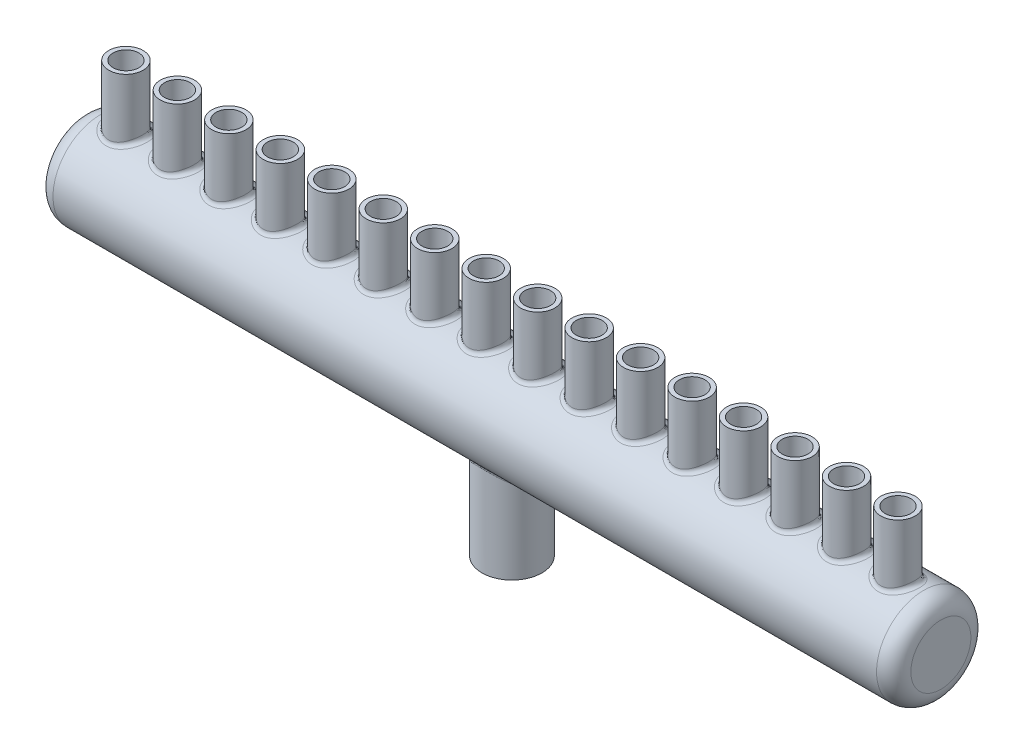
SolidWorks part; units mm, degrees
ref_plane "Alzado" through (0, 0, 0) normal (0, 0, 1) x (1, 0, 0)
ref_plane "Planta" through (0, 0, 0) normal (0, 1, 0) x (1, 0, 0)
ref_plane "Vista lateral" through (0, 0, 0) normal (1, 0, 0) x (0, 0, -1)
sketch "Croquis1" plane through (0, 0, 0) normal (1, 0, 0) x (0, 0, -1)
  circle A0 centre (0, 0) radius 11
  dimension "D1" = 22
extrude "Extruir1" add sketch "Croquis1" along normal mid plane 200
sketch "Croquis2" plane through (0, 0, 0) normal (0, 1, 0) x (1, 0, 0)
  circle A0 centre (0, 0) radius 7
  dimension "D1" = 14
extrude "Extruir2" add sketch "Croquis2" against normal blind 30
sketch "Croquis3" plane through (0, 0, 0) normal (0, 1, 0) x (1, 0, 0)
  line L0 (0, 0) -> (-100, 0) construction
  line L1 (-100, 11) -> (-100, -11) construction
  line L2 (0, 0) -> (0, 11) construction
  line L3 (100, 11) -> (-100, 11) construction
  circle A0 centre (-6, 0) radius 4
  circle A1 centre (-18, 0) radius 4
  circle A2 centre (-30, 0) radius 4
  circle A3 centre (-42, 0) radius 4
  circle A4 centre (-54, 0) radius 4
  circle A5 centre (-66, 0) radius 4
  circle A6 centre (-78, 0) radius 4
  circle A7 centre (-90, 0) radius 4
  circle A8 centre (90, 0) radius 4
  circle A9 centre (78, 0) radius 4
  circle A10 centre (66, 0) radius 4
  circle A11 centre (54, 0) radius 4
  circle A12 centre (42, 0) radius 4
  circle A13 centre (30, 0) radius 4
  circle A14 centre (18, 0) radius 4
  circle A15 centre (6, 0) radius 4
  dimension "D1" = 8
  dimension "D2" = 6
extrude "Extruir3" add sketch "Croquis3" along normal blind 25
fillet "Redondeo1" radius 4 2 edges at (100, 0, -11) (-100, 0, -11)
fillet "Redondeo2" radius 1 17 edges at (6.6419, 10.267, 3.9482) (30.6419, 10.267, 3.9482) (54.6419, 10.267, 3.9482) (78.6419, 10.267, 3.9482) (-89.3581, 10.267, 3.9482) (-65.3581, 10.267, 3.9482) (-41.3581, 10.267, 3.9482) (-17.3581, 10.267, 3.9482) (-1.662, -8.6465, -6.7998) (-5.3581, 10.267, 3.9482) (-29.3581, 10.267, 3.9482) (-53.3581, 10.267, 3.9482) (-77.3581, 10.267, 3.9482) (90.6419, 10.267, 3.9482) (66.6419, 10.267, 3.9482) (42.6419, 10.267, 3.9482) (18.6419, 10.267, 3.9482)
shell "Vaciado1" thickness 1 removed face at (0, -30, 7) removed face at (90, 25, -4) removed face at (78, 25, -4) removed face at (66, 25, -4) removed face at (54, 25, -4) removed face at (42, 25, -4) removed face at (30, 25, -4) removed face at (18, 25, -4) removed face at (6, 25, -4) removed face at (-6, 25, 4) removed face at (-18, 25, 4) removed face at (-30, 25, 4) removed face at (-42, 25, 4) removed face at (-54, 25, 4) removed face at (-66, 25, 4) removed face at (-78, 25, 4) removed face at (-90, 25, 4)
